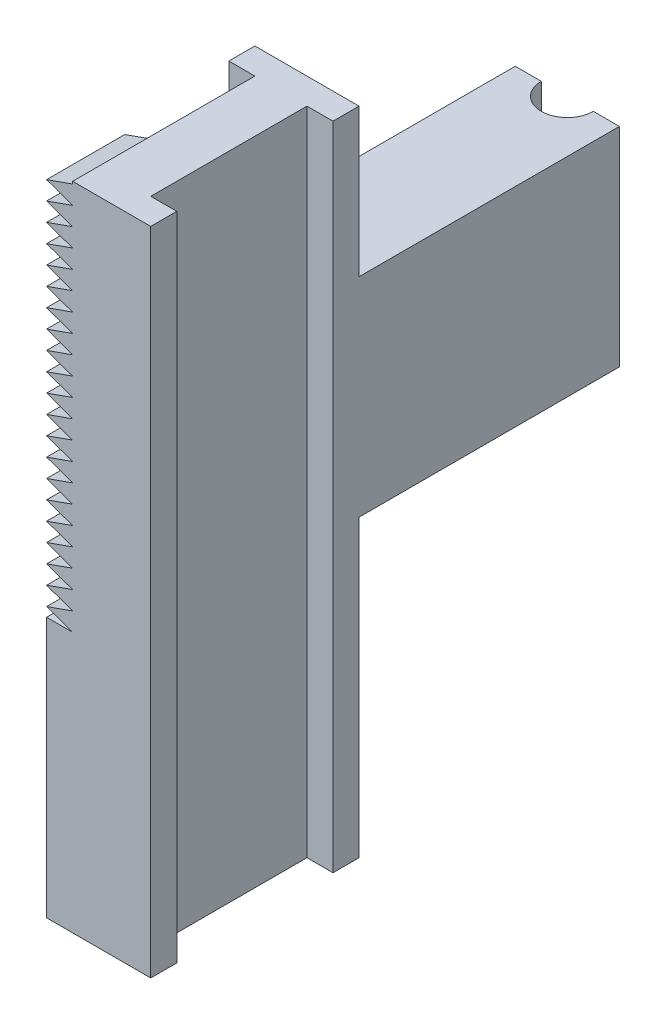
SolidWorks part; units mm, degrees
ref_plane "Front Plane" through (0, 0, 0) normal (0, 0, 1) x (1, 0, 0)
ref_plane "Top Plane" through (0, 0, 0) normal (0, 1, 0) x (1, 0, 0)
ref_plane "Right Plane" through (0, 0, 0) normal (1, 0, 0) x (0, 0, -1)
sketch "Sketch1" plane through (0, 0, 0) normal (0, 1, 0) x (1, 0, 0)
  line L0 (0, 0) -> (0, 4) construction
  line L1 (2, 4) -> (-2, 4)
  line L2 (-2, 4) -> (-2, 3)
  line L3 (-2, 3) -> (-1, 3)
  line L4 (-1, 3) -> (-1, 0)
  line L5 (-1, 0) -> (0, 0) construction
  line L6 (1, 3) -> (1, 0)
  line L7 (2, 3) -> (1, 3)
  line L8 (2, 4) -> (2, 3)
  line L9 (-1, 0) -> (1, 0)
  dimension "D1" = 4
  dimension "D2" = 2
  dimension "D3" = 1
  dimension "D4" = 1
extrude "Boss-Extrude1" add sketch "Sketch1" along normal blind 25
mirror "Mirror1" about plane through (-1, 25, 0) normal (0, 0, -1) of "Boss-Extrude1"
sketch "Sketch2" plane through (0, 25, 0) normal (0, 1, 0) x (1, 0, 0)
  line L1 (-1, -3) -> (-2, -3)
  line L2 (-1, -3) -> (-1, -4)
  line L3 (-1, -4) -> (-2, -4)
  line L4 (-2, -3) -> (-2, -4)
extrude "Cut-Extrude1" cut sketch "Sketch2" against normal blind 15
sketch "Sketch3" plane through (0, 0, 4) normal (0, 0, 1) x (1, 0, 0)
  line L0 (-1, 10) -> (-2, 10.355)
  line L1 (-1, 10) -> (-1, 10.355) construction
  line L2 (-1, 10) -> (-1, 25) construction
  line L3 (-1, 10.355) -> (-2, 10.355) construction
  line L4 (-1, 10.71) -> (-2, 10.355)
  line L5 (-1, 10.71) -> (-1, 10)
  dimension "D1" = 1
  dimension "D2" = 0.355
extrude "Boss-Extrude2" add sketch "Sketch3" against normal blind 3
pattern_linear "LPattern1" count 21 spacing 0.71 along (0, 1, 0) of "Boss-Extrude2"
sketch "Sketch4" plane through (0, 0, -4) normal (0, 0, -1) x (-1, 0, 0)
  line L0 (0, 21.9615) -> (0, 8.6905) construction
  line L2 (2, 11.326) -> (-2, 11.326)
  line L3 (2, 11.326) -> (2, 19.326)
  line L4 (2, 19.326) -> (-2, 19.326)
  line L5 (-2, 11.326) -> (-2, 19.326)
  line L6 (2, 11.326) -> (-2, 19.326) construction
  line L7 (2, 19.326) -> (-2, 11.326) construction
  point P3 (0, 15.326)
  point P8 (0, 0)
  dimension "D1" = 4
  dimension "D2" = 8
extrude "Boss-Extrude3" add sketch "Sketch4" along normal blind 10 contours L4 L5 L2 L3
sketch "Sketch5" plane through (0, 19.326, 0) normal (0, 1, 0) x (1, 0, 0)
  line L0 (-2, 14) -> (2, 14) construction
  circle A0 centre (0, 14) radius 1
  dimension "D1" = 2
extrude "Cut-Extrude2" cut sketch "Sketch5" against normal blind 7 contours A0
